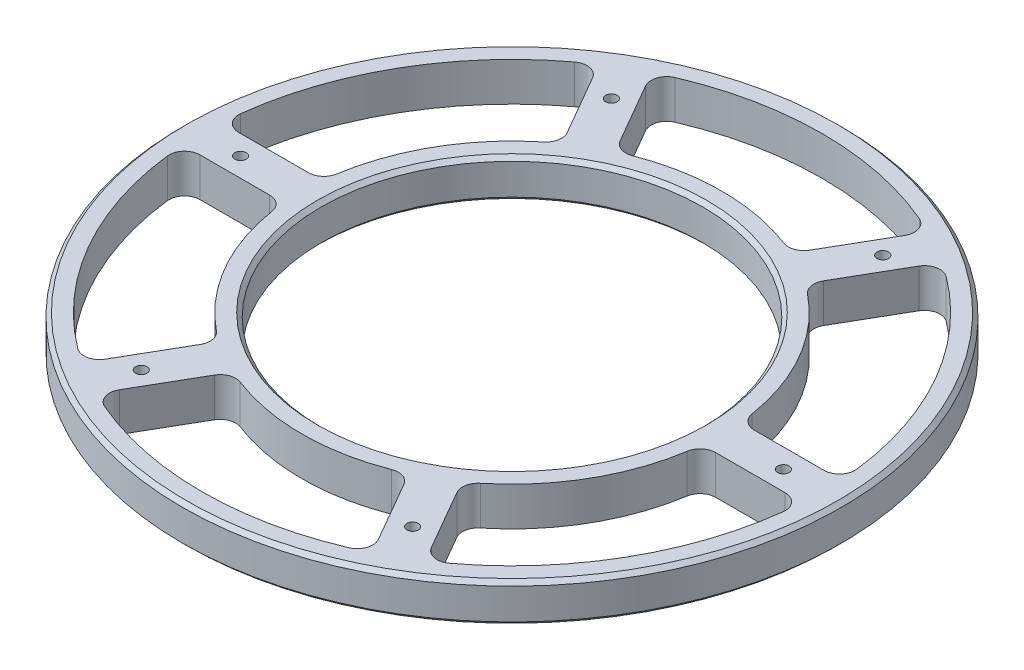
SolidWorks part; units mm, degrees
ref_plane "Front Plane" through (0, 0, 0) normal (0, 0, 1) x (1, 0, 0)
ref_plane "Top Plane" through (0, 0, 0) normal (0, 1, 0) x (1, 0, 0)
ref_plane "Right Plane" through (0, 0, 0) normal (1, 0, 0) x (0, 0, -1)
sketch "Sketch2" plane through (0, 0, 0) normal (1, 0, 0) x (0, 0, -1)
  line L0 (-49.2125, 0) -> (-84.9998, 0)
  line L1 (-84.9998, 0) -> (-84.9998, 10)
  line L2 (-84.9998, 10) -> (-49.2125, 10)
  line L3 (-49.2125, 10) -> (-49.2125, 0)
  dimension "D1" = 84.9998
  dimension "D2" = 10
  dimension "D4" = 49.2125
ref_axis "Axis1" through (0, -0.75, 0) along (0, 1, 0)
revolve "Revolve1" add sketch "Sketch2" angle 360 about axis through (0, -0.75, 0) along (0, 1, 0)
hole_wizard "#32 (0.116) Diameter Hole1" positions "Sketch6" profile "Sketch7" hole size "#32" standard "ANSI Inch" end condition through all
sketch "Sketch6" plane through (0, 10, 0) normal (0, 1, 0) x (1, 0, 0)
  line L0 (0, 0) -> (-69.8201, 120.932) construction
  line L2 (0, 0) -> (0, 109.0908) construction
  point P0 (-35, 60.6218)
  dimension "D1" = 30
  dimension "D2" = 70
sketch "Sketch7" plane through (-35, 10, -60.6218) normal (1, 0, 0) x (0, 0, 1)
  line L0 (0, 0) -> (0, 10)
  line L1 (0, 10) -> (1.4732, 10)
  line L2 (1.4732, 10) -> (1.4732, 0)
  line L5 (1.4732, 0) -> (0, 0)
  line L11 (0, -6.35) -> (0, 107.95) construction
  dimension "Thru Hole Dia." = 2.9464
  dimension "Thru Hole Depth" = 10
pattern_circular "CirPattern3" count 6 over 360 about axis through (0, -0.75, 0) along (0, 1, 0) of "#32 (0.116) Diameter Hole1"
sketch "Sketch8" plane through (0, 10, 0) normal (0, 1, 0) x (1, 0, 0)
  line L4 (0, 0) -> (0, 93.9995) construction
  line L5 (-22.6606, 49.2493) -> (-35.5916, 71.6464)
  line L6 (22.6606, 49.2493) -> (35.5916, 71.6464)
  line L7 (0, 0) -> (-35, 60.6218) construction
  arc A0 (-22.6606, 49.2493) -> (22.6606, 49.2493) centre (0, 0) cw
  arc A1 (-35.5916, 71.6464) -> (35.5916, 71.6464) centre (0, 0) cw
  circle A2 centre (0, 0) radius 84.9998 construction
  circle A4 centre (0, 0) radius 49.2125 construction
  point P4 (0, 0)
  point P16 (-40.518, 88.0596)
  point P17 (0, 0)
  dimension "D1" = 5
  dimension "D2" = 5
  dimension "D3" = 5
extrude "Cut-Extrude1" cut sketch "Sketch8" against normal through all
fillet "Fillet1" radius 4 4 edges at (-22.6606, 5, -49.2493) (22.6606, 5, -49.2493) (35.5916, 5, -71.6464) (-35.5916, 5, -71.6464)
pattern_circular "CirPattern4" count 6 over 360 about axis through (0, -0.75, 0) along (0, 1, 0) of "Cut-Extrude1", "Fillet1"
chamfer "Chamfer1" distance 1 angle 45 2 edges at (0, 10, -49.2125) (0, 0, -49.2125)
chamfer "Chamfer2" distance 1 angle 45 2 edges at (0, 10, -84.9998) (0, 0, -84.9998)
